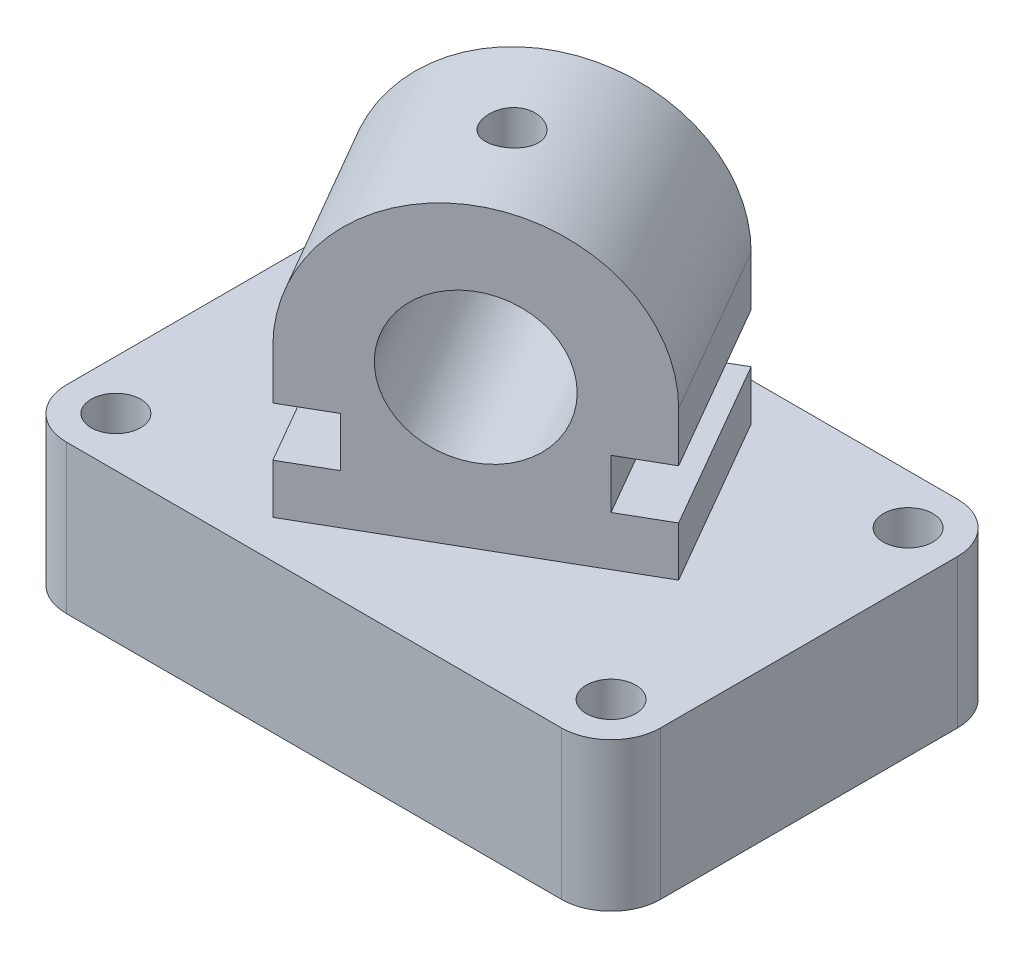
SolidWorks part; units mm, degrees
ref_plane "Front Plane" through (0, 0, 0) normal (0, 0, 1) x (1, 0, 0)
ref_plane "Top Plane" through (0, 0, 0) normal (0, 1, 0) x (1, 0, 0)
ref_plane "Right Plane" through (0, 0, 0) normal (1, 0, 0) x (0, 0, -1)
sketch "Sketch1" plane through (0, 0, 0) normal (0, 1, 0) x (1, 0, 0)
  line L0 (-38.1, 0) -> (38.1, 0) construction
  line L1 (-31.75, 25.4) -> (31.75, 25.4)
  line L2 (-38.1, 19.05) -> (-38.1, -19.05)
  line L3 (-31.75, -25.4) -> (31.75, -25.4)
  line L4 (38.1, 19.05) -> (38.1, -19.05)
  line L5 (0, 25.4) -> (0, -25.4) construction
  arc A0 (-38.1, -19.05) -> (-31.75, -25.4) centre (-31.75, -19.05) ccw
  arc A1 (31.75, -25.4) -> (38.1, -19.05) centre (31.75, -19.05) ccw
  arc A2 (31.75, 25.4) -> (38.1, 19.05) centre (31.75, 19.05) cw
  arc A3 (-31.75, 25.4) -> (-38.1, 19.05) centre (-31.75, 19.05) ccw
  circle A4 centre (-31.75, 19.05) radius 3.175
  circle A5 centre (31.75, 19.05) radius 3.175
  circle A6 centre (31.75, -19.05) radius 3.175
  circle A7 centre (-31.75, -19.05) radius 3.175
  point P6 (-38.1, -25.4)
  point P11 (38.1, 25.4)
  point P14 (-38.1, 25.4)
  dimension "D3" = 6.35
  dimension "D4" = 6.35
  dimension "D1" = 76.2
  dimension "D2" = 50.8
extrude "Boss-Extrude1" add sketch "Sketch1" along normal blind 19.05
ref_axis "Axis1" through (0, 19.4181, 0) along (0, -1, 0)
ref_plane "Plane1" through (0, 0, 0) normal (0.5, 0, 0.866) x (0, -1, 0)
sketch "Sketch2" plane through (0, 0, 0) normal (0.5, 0, 0.866) x (0, -1, 0)
  line L0 (-19.05, 40.1963) -> (-19.05, -14.7963) construction
  line L1 (-19.05, 19.05) -> (-19.05, -19.05)
  line L2 (0, 0) -> (-43.9917, 0) construction
  line L3 (-19.05, 19.05) -> (-25.4, 19.05)
  line L4 (-19.05, -19.05) -> (-25.4, -19.05)
  line L5 (-25.4, 19.05) -> (-25.4, 12.7)
  line L6 (-25.4, -19.05) -> (-25.4, -12.7)
  line L7 (-25.4, 12.7) -> (-31.75, 12.7)
  line L8 (-25.4, -12.7) -> (-31.75, -12.7)
  line L9 (-31.75, 12.7) -> (-31.75, 19.05)
  line L10 (-31.75, -12.7) -> (-31.75, -19.05)
  line L11 (-31.75, 19.05) -> (-38.1, 19.05)
  line L12 (-31.75, -19.05) -> (-38.1, -19.05)
  arc A0 (-38.1, -19.05) -> (-38.1, 19.05) centre (-38.1, 0) cw
  circle A1 centre (-38.1, 0) radius 9.525
  dimension "D6" = 19.05
  dimension "D1" = 38.1
  dimension "D2" = 19.05
  dimension "D3" = 6.35
  dimension "D4" = 6.35
  dimension "D5" = 6.35
extrude "Boss-Extrude2" add sketch "Sketch2" along normal mid plane 25.4
ref_plane "Plane2" through (0, 57.15, 0) normal (0, 1, 0) x (1, 0, 0)
sketch "Sketch3" plane through (0, 57.15, 0) normal (0, 1, 0) x (1, 0, 0)
  circle A0 centre (0, 0) radius 3.175
extrude "Cut-Extrude1" cut sketch "Sketch3" against normal up to next
